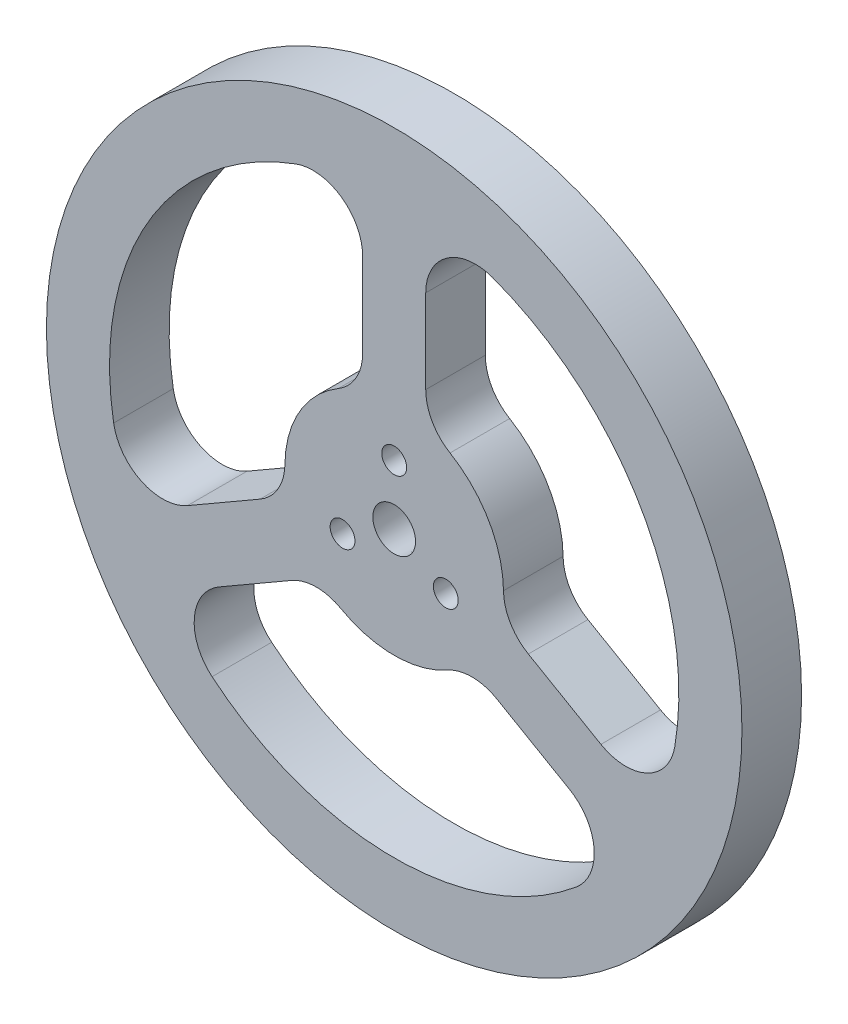
SolidWorks part; units mm, degrees
material "AISI 304"
ref_plane "Front Plane" through (0, 0, 0) normal (0, 0, 1) x (1, 0, 0)
ref_plane "Top Plane" through (0, 0, 0) normal (0, 1, 0) x (1, 0, 0)
ref_plane "Right Plane" through (0, 0, 0) normal (1, 0, 0) x (0, 0, -1)
sketch "Sketch1" plane through (0, 0, 0) normal (0, 0, 1) x (1, 0, 0)
  line L0 (0, 0) -> (28.65, 0) construction
  line L1 (28.65, 0) -> (35, 0) construction
  circle A0 centre (0, 0) radius 35
  circle A1 centre (0, 0) radius 28.65
  dimension "D1" = 70
  dimension "D2" = 6.35
extrude "MainBody" add sketch "Sketch1" along normal blind 6
sketch "Sketch2" plane through (0, 0, 6) normal (0, 0, 1) x (1, 0, 0)
  line L0 (0, 0) -> (0, 28.65) construction
  line L1 (0, 0) -> (24.8116, -14.325) construction
  line L2 (0, 0) -> (-24.8116, -14.325) construction
  line L3 (-3.175, 28.4735) -> (-3.175, 1.8331)
  line L4 (-3.175, 1.8331) -> (-26.2463, -11.4871)
  line L5 (0, -3.6662) -> (-23.0713, -16.9864)
  line L6 (0, -3.6662) -> (23.0713, -16.9864)
  line L7 (3.175, 28.4735) -> (3.175, 1.8331)
  line L8 (3.175, 1.8331) -> (26.2463, -11.4871)
  line L9 (0, 0) -> (0, -3.6662) construction
  line L10 (-3.175, 1.8331) -> (0, 1.8331) construction
  line L11 (0, 1.8331) -> (3.175, 1.8331) construction
  line L12 (-14.7106, -4.827) -> (-13.1231, -7.5767) construction
  line L13 (-13.1231, -7.5767) -> (-11.5356, -10.3263) construction
  circle A0 centre (0, 0) radius 28.65 construction
  arc A1 (-26.2463, -11.4871) -> (-23.0713, -16.9864) centre (0, 0) ccw
  arc A2 (23.0713, -16.9864) -> (26.2463, -11.4871) centre (0, 0) ccw
  arc A3 (3.175, 28.4735) -> (-3.175, 28.4735) centre (0, 0) ccw
  dimension "D1" = 120
  dimension "D2" = 120
  dimension "D3" = 6.35
  dimension "D4" = 6.35
extrude "Supports" add sketch "Sketch2" against normal up to surface (6 mm away) up to face at (35, 0, 0)
sketch "Sketch3" plane through (0, 0, 6) normal (0, 0, 1) x (1, 0, 0)
  circle A0 centre (0, 0) radius 5
  dimension "D1" = 10
extrude "ShaftHoleMaterial" add sketch "Sketch3" against normal up to surface (6 mm away) up to face at (-14.2324, 8.2171, 0)
sketch "Sketch4" plane through (0, 0, 6) normal (0, 0, 1) x (1, 0, 0)
  arc A0 (4.9326, 0.8184) -> (3.175, 3.8626) centre (0, 0) ccw construction
  circle A1 centre (0, 0) radius 5 construction
  circle A2 centre (0, 0) radius 11
  dimension "D1" = 22
extrude "Boss-Extrude1" add sketch "Sketch4" against normal up to surface (6 mm away) up to face at (-11.9765, 6.9147, 0)
sketch "Sketch5" plane through (0, 0, 0) normal (1, 0, 0) x (0, 0, -1)
  line L0 (0, 0) -> (-6, 0)
  line L1 (-6, 28.4735) -> (-6, 10.5318) construction
  line L2 (-6, 0) -> (-6, 2.15)
  line L3 (-6, 2.15) -> (0, 2.15) construction
  line L4 (0, 2.15) -> (0, 0)
  line L5 (-6, 2.15) -> (0, 2.6749)
  line L6 (0, 2.6749) -> (0, 2.15)
  dimension "D1" = 2.15
  dimension "D2" = 5
revolve "KeylessBushingBore" cut sketch "Sketch5" angle 360 about L0
hole_wizard "M3 Tapped Hole1" positions "3DSketch1" profile "Sketch6" tap size "M3" standard "ISO"
sketch3d "3DSketch1"
  line L0 (0, 0, 0) -> (0, 6, 0) construction
  line L2 (0, 0, 0) -> (-5.1962, -3, 0) construction
  line L4 (0, 0, 0) -> (5.1962, -3, 0) construction
  circle A1 centre (0, 0, 0) radius 6 construction
  point P0 (5.1962, -3, 0)
  point P2 (0, 6, 0)
  point P4 (-5.1962, -3, 0)
  point P12 (0, 0, 6)
  dimension "D1" = 12
  dimension "D2" = 120
  dimension "D3" = 120
sketch "Sketch6" plane through (5.1962, -3, 0) normal (1, 0, 0) x (0, 1, 0)
  line L0 (0, 0) -> (0, 9.2511)
  line L1 (0, 9.2511) -> (1.25, 8.5)
  line L2 (1.25, 8.5) -> (1.25, 0)
  line L5 (1.25, 0) -> (0, 0)
  line L10 (0, 9.2511) -> (-1.25, 8.5) construction
  line L11 (0, -6.35) -> (0, 107.95) construction
  dimension "Tap Drill Dia." = 2.5
  dimension "Tap Drill Depth" = 8.5
  dimension "Drill Angle" = 118
cosmetic thread "Hole Thread1" parameters "D1"=6, "D2"=3
cosmetic thread "Hole Thread2" parameters "D1"=6, "D2"=3
cosmetic thread "Hole Thread3" parameters "D1"=6, "D2"=3
fillet "Fillet1" radius 5 12 edges at (10.7083, -2.5163, 3) (7.5333, -8.0155, 3) (-23.0713, -16.9864, 3) (-7.5333, -8.0155, 3) (3.175, 10.5318, 3) (3.175, 28.4735, 3) (26.2463, -11.4871, 3) (23.0713, -16.9864, 3) (-26.2463, -11.4871, 3) (-3.175, 28.4735, 3) (-3.175, 10.5318, 3) (-10.7083, -2.5163, 3)
